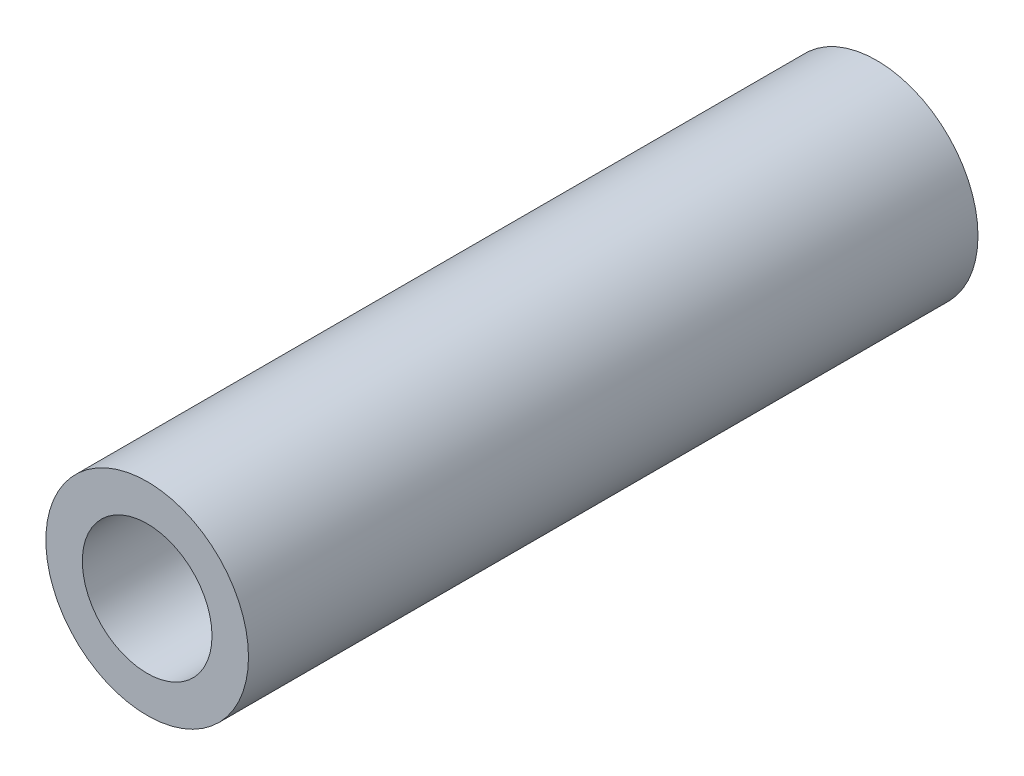
SolidWorks part; units mm, degrees
ref_plane "Front Plane" through (0, 0, 0) normal (0, 0, 1) x (1, 0, 0)
ref_plane "Top Plane" through (0, 0, 0) normal (0, 1, 0) x (1, 0, 0)
ref_plane "Right Plane" through (0, 0, 0) normal (1, 0, 0) x (0, 0, -1)
sketch "Sketch1" plane through (0, 0, 0) normal (0, 0, 1) x (1, 0, 0)
  circle A0 centre (33, 0) radius 2.5
  dimension "D1" = 5
extrude "Boss-Extrude1" add sketch "Sketch1" along normal blind 18
sketch "Sketch3" plane through (0, 0, 18) normal (0, 0, 1) x (1, 0, 0)
  circle A0 centre (33, 0) radius 1.6
  circle A1 centre (33, 0) radius 2.1
  dimension "D1" = 3.2
  dimension "D2" = 4.2
extrude "Cut-Extrude1" cut sketch "Sketch3" against normal up to next contours A0
equation "\"RingPostIn\"=5"
equation "\"D1@Sketch1\"=\"RingPostIn\""
equation "\"RingPinShaft\"= 5"
equation "\"CenterBearingOut\"=32"
equation "\"m3Thru\"=3.2"
equation "\"D1@Sketch3\"=\"m3Thru\""
equation "\"m3Insert\"=4.2"
equation "\"D2@Sketch3\"=\"m3Insert\""
